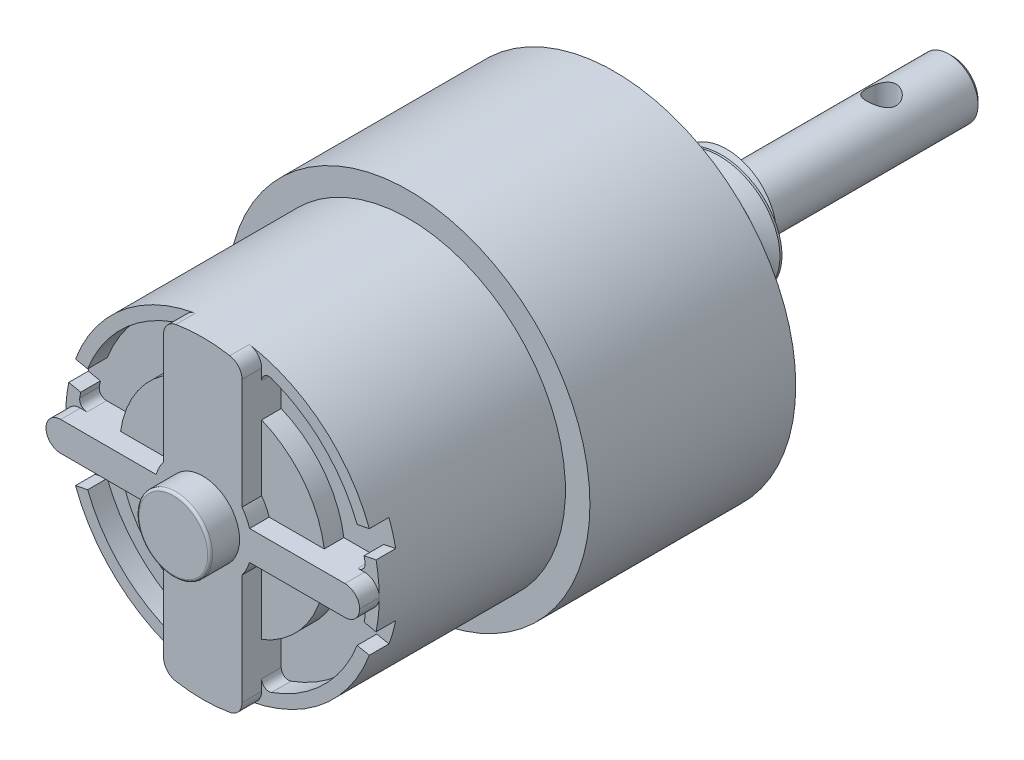
SolidWorks part; units mm, degrees
material "PET"
ref_plane "Front Plane" through (0, 0, 0) normal (0, 0, 1) x (1, 0, 0)
ref_plane "Top Plane" through (0, 0, 0) normal (0, 1, 0) x (1, 0, 0)
ref_plane "Right Plane" through (0, 0, 0) normal (1, 0, 0) x (0, 0, -1)
sketch "Sketch1" plane through (0, 0, 0) normal (0, 0, 1) x (1, 0, 0)
  circle A0 centre (0, 0) radius 16
  dimension "D1" = 32
extrude "Boss-Extrude1" add sketch "Sketch1" along normal blind 21
sketch "Sketch2" plane through (0, 0, 21) normal (0, 0, 1) x (1, 0, 0)
  circle A0 centre (0, 0) radius 16
  dimension "D1" = 32
extrude "Boss-Extrude2" add sketch "Sketch2" along normal blind 19
sketch "Sketch3" plane through (0, 0, 40) normal (0, 0, 1) x (1, 0, 0)
  line L0 (-4, -15.4919) -> (-4, -1.5)
  line L4 (4, -15.4919) -> (4, -1.5)
  line L5 (4, -1.5) -> (15.9295, -1.5)
  line L6 (-15.9295, -1.5) -> (-4, -1.5)
  line L7 (-15.9295, 1.5) -> (-4, 1.5)
  line L8 (4, 1.5) -> (4, 15.4919)
  line L9 (-4, 1.5) -> (-4, 15.4919)
  line L12 (4, 1.5) -> (15.9295, 1.5)
  arc A0 (-15.9295, 1.5) -> (-15.9295, -1.5) centre (0, 0) ccw
  arc A2 (4, 15.4919) -> (-4, 15.4919) centre (0, 0) ccw
  arc A3 (15.9295, -1.5) -> (15.9295, 1.5) centre (0, 0) ccw
  arc A4 (-4, -15.4919) -> (4, -15.4919) centre (0, 0) ccw
  point P10 (-20.25, 0)
  point P11 (20.25, 0)
  point P15 (-20.25, -1.5)
  point P16 (20.25, -1.5)
  point P17 (-20.25, 1.5)
  point P18 (20.25, 1.5)
extrude "Boss-Extrude3" add sketch "Sketch3" along normal blind 2
ref_plane "Plane1" through (0, 0, 40) normal (0, 0, 1) x (1, 0, 0)
sketch "Sketch4" plane through (0, 0, 40) normal (0, 0, 1) x (1, 0, 0)
  line L0 (10.3923, 1.5) -> (13.818, 1.5)
  line L1 (0, 0) -> (5.4478, 0) construction
  line L2 (0, 0) -> (0, -4.6183) construction
  line L3 (4, 13.1696) -> (4, 9.7082)
  line L4 (14.9913, -5.5911) -> (13.7497, -5.3393)
  line L5 (14.4557, -2.9316) -> (15.6808, -3.1801)
  line L6 (14.4557, 2.9316) -> (15.6808, 3.1801)
  line L7 (4, -13.1696) -> (4, -9.7082)
  line L8 (14.9913, 5.5911) -> (13.7497, 5.3393)
  line L9 (10.3923, -1.5) -> (13.818, -1.5)
  line L10 (-14.9913, 5.5911) -> (-13.7497, 5.3393)
  line L11 (-14.4557, 2.9316) -> (-15.6808, 3.1801)
  line L12 (-14.4557, -2.9316) -> (-15.6808, -3.1801)
  line L13 (-14.9913, -5.5911) -> (-13.7497, -5.3393)
  line L14 (-10.3923, -1.5) -> (-13.818, -1.5)
  line L15 (-4, -13.1696) -> (-4, -9.7082)
  line L16 (-4, 13.1696) -> (-4, 9.7082)
  line L17 (-10.3923, 1.5) -> (-13.818, 1.5)
  arc A0 (10.3923, 1.5) -> (4, 9.7082) centre (0, 0) ccw
  arc A1 (14.5583, 2.3705) -> (14.4557, 2.9316) centre (0, 0) ccw
  arc A3 (14.5583, 2.3705) -> (13.818, 1.5) centre (13.818, 2.25) cw
  arc A4 (5.0045, 13.8751) -> (4, 13.1696) centre (4.75, 13.1696) ccw
  arc A5 (15.9295, 1.5) -> (4, 15.4919) centre (0, 0) ccw construction
  arc A6 (13.7497, 5.3393) -> (5.0045, 13.8751) centre (0, 0) ccw
  arc A7 (15.6808, 3.1801) -> (14.9913, 5.5911) centre (0, 0) ccw
  arc A8 (5.0045, -13.8751) -> (4, -13.1696) centre (4.75, -13.1696) cw
  arc A9 (15.6808, -3.1801) -> (14.9913, -5.5911) centre (0, 0) cw
  arc A10 (13.7497, -5.3393) -> (5.0045, -13.8751) centre (0, 0) cw
  arc A11 (14.5583, -2.3705) -> (13.818, -1.5) centre (13.818, -2.25) ccw
  arc A12 (14.5583, -2.3705) -> (14.4557, -2.9316) centre (0, 0) cw
  arc A13 (10.3923, -1.5) -> (4, -9.7082) centre (0, 0) cw
  arc A14 (-14.5583, -2.3705) -> (-14.4557, -2.9316) centre (0, 0) ccw
  arc A15 (-14.5583, -2.3705) -> (-13.818, -1.5) centre (-13.818, -2.25) cw
  arc A16 (-15.6808, -3.1801) -> (-14.9913, -5.5911) centre (0, 0) ccw
  arc A17 (-15.6808, 3.1801) -> (-14.9913, 5.5911) centre (0, 0) cw
  arc A18 (-14.5583, 2.3705) -> (-13.818, 1.5) centre (-13.818, 2.25) ccw
  arc A19 (-14.5583, 2.3705) -> (-14.4557, 2.9316) centre (0, 0) cw
  arc A20 (-10.3923, -1.5) -> (-4, -9.7082) centre (0, 0) ccw
  arc A21 (-13.7497, -5.3393) -> (-5.0045, -13.8751) centre (0, 0) ccw
  arc A22 (-5.0045, -13.8751) -> (-4, -13.1696) centre (-4.75, -13.1696) ccw
  arc A23 (-13.7497, 5.3393) -> (-5.0045, 13.8751) centre (0, 0) cw
  arc A24 (-5.0045, 13.8751) -> (-4, 13.1696) centre (-4.75, 13.1696) cw
  arc A25 (-10.3923, 1.5) -> (-4, 9.7082) centre (0, 0) cw
  dimension "D1" = 1.25
  dimension "D2" = 4.25
  dimension "D3" = 0.75
  dimension "D5" = 1.25
extrude "Cut-Extrude1" cut sketch "Sketch4" against normal blind 2
sketch "Sketch5" plane through (0, 0, 42) normal (0, 0, 1) x (1, 0, 0)
  circle A0 centre (0, 0) radius 3.75
  dimension "D1" = 7.5
extrude "Boss-Extrude4" add sketch "Sketch5" along normal blind 3
fillet "Fillet1" radius 0.25 1 edges at (3.75, 0, 45)
fillet "Fillet2" radius 1.5 8 edges
ref_plane "Plane2" through (0, 0, 40) normal (0, 0, 1) x (1, 0, 0)
sketch "Sketch6" plane through (0, 0, 40) normal (0, 0, 1) x (1, 0, 0)
  circle A0 centre (0, 0) radius 5
  dimension "D1" = 10
extrude "Boss-Extrude5" add sketch "Sketch6" along normal blind 2
sketch "Sketch7" plane through (0, 0, 0) normal (0, 0, -1) x (-1, 0, 0)
  circle A0 centre (0, 0) radius 6
  dimension "D1" = 12
extrude "Boss-Extrude6" add sketch "Sketch7" along normal blind 12
sketch "Sketch8" plane through (0, 0, -12) normal (0, 0, -1) x (-1, 0, 0)
  circle A0 centre (0, 0) radius 3
  dimension "D1" = 6
extrude "Boss-Extrude7" add sketch "Sketch8" along normal blind 22.5
sketch "Sketch9" plane through (0, 0, 0) normal (0, 1, 0) x (1, 0, 0)
  line L0 (0, 34.5) -> (0, 27.25) construction
  line L1 (3, 34.5) -> (-3, 34.5) construction
  circle A0 centre (0, 27.25) radius 1.5
  dimension "D2" = 3
  dimension "D1" = 7.25
extrude "Cut-Extrude2" cut sketch "Sketch9" against normal blind 10 and the other way blind 10
chamfer "Chamfer1" distance 0.4 angle 45 1 edges at (-3, 0, -34.5)
ref_plane "Plane3" through (0, 0, -15) normal (0, 0, -1) x (-1, 0, 0)
sketch "Sketch10" plane through (0, 0, -15) normal (0, 0, -1) x (-1, 0, 0)
  circle A0 centre (0, 0) radius 6
curve "Helix/Spiral1" pitch 2 height 18 radius 6 centre (0, 0, -15) axis (0, 0, 1) start towards (-1, 0, 0)
ref_plane "Plane4" through (0, 0, 0) normal (0, 1, 0) x (1, 0, 0)
sketch "Sketch11" plane through (0, 0, 0) normal (0, 1, 0) x (1, 0, 0)
  line L3 (6, 0) -> (6, 12) construction
  line L7 (4.4412, 15.9831) -> (6, 15.0831)
  line L8 (6, 15.0831) -> (6, 16.8831)
  line L9 (6, 16.8831) -> (4.4412, 15.9831)
  circle A1 centre (5.4804, 15.9831) radius 0.5196 construction
  dimension "D3" = 1.8
sweep "Cut-Sweep5" cut profiles "Sketch11" path "Helix/Spiral1" align with end faces yes
sketch "Sketch12" plane through (0, 0, 0) normal (0, 0, -1) x (-1, 0, 0)
  circle A0 centre (0, 0) radius 6
extrude "Boss-Extrude8" add sketch "Sketch12" against normal blind 4
sketch "Sketch13" plane through (0, 0, 0) normal (0, 0, -1) x (-1, 0, 0)
  circle A0 centre (0, 0) radius 18.5
  dimension "D1" = 37
extrude "Boss-Extrude9" add sketch "Sketch13" against normal blind 21
